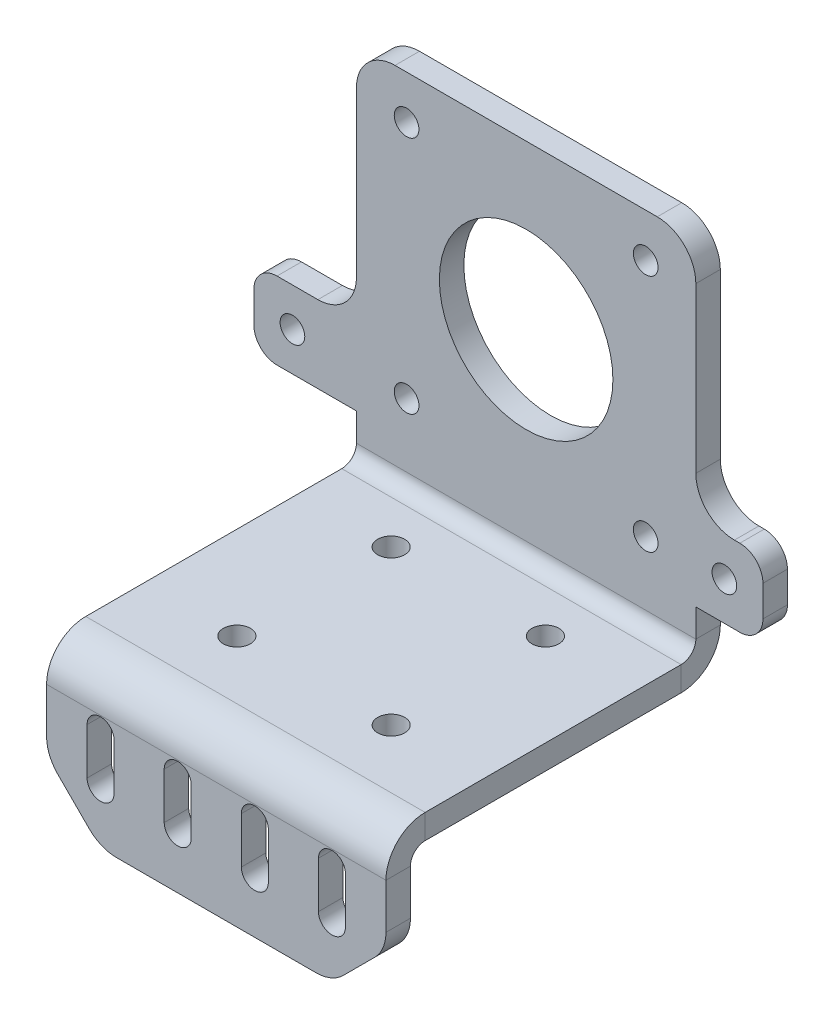
SolidWorks part; units mm, degrees
note: The reader was unsure of these and kept them because the rebuilt part matched: flange length of "Edge-Flange1", "Edge-Flange2".
material "5052-H32"
ref_plane "Front Plane" through (0, 0, 0) normal (0, 0, 1) x (1, 0, 0)
ref_plane "Top Plane" through (0, 0, 0) normal (0, 1, 0) x (1, 0, 0)
ref_plane "Right Plane" through (0, 0, 0) normal (1, 0, 0) x (0, 0, -1)
sketch "Sketch1" plane through (0, 0, 0) normal (0, 1, 0) x (1, 0, 0)
  line L1 (-22, -18.5) -> (22, -18.5)
  line L2 (-22, -18.5) -> (-22, 18.5)
  line L3 (-22, 18.5) -> (22, 18.5)
  line L4 (22, -18.5) -> (22, 18.5)
  line L5 (0, 18.5) -> (0, -18.5) construction
  line L6 (-22, 0) -> (22, 0) construction
  line L7 (-10, -9) -> (10, -9) construction
  line L8 (-10, -9) -> (-10, 11) construction
  line L9 (-10, 11) -> (10, 11) construction
  line L10 (10, -9) -> (10, 11) construction
  line L11 (0, 11) -> (0, -9) construction
  line L12 (-10, 1) -> (10, 1) construction
  circle A0 centre (-10, 11) radius 1.75
  circle A1 centre (10, 11) radius 1.75
  circle A2 centre (10, -9) radius 1.75
  circle A3 centre (-10, -9) radius 1.75
  point P0 (0, 0)
  point P4 (0, 0)
  dimension "D3" = 3.5
  dimension "D1" = 18.5
  dimension "D2" = 44
  dimension "D4" = 20
  dimension "D5" = 1
base flange "Base-Flange1" sketch "Sketch1" thickness 3.175 reverse thickness direction no parameters "D1"=1.905
edge flange "Edge-Flange1" sketch "Sketch8" flange angle 90 flange length 50 flange position material outside bend radius 1.905 thickness 3.175 relief rectangular parameters "D6"=10
sketch "Sketch8" plane through (0, 0, -18.5) normal (0, 0, -1) x (-1, 0, 0)
  line L0 (-22, 0) -> (22, 0) construction
  line L1 (-22, 0) -> (22, 0)
  line L2 (-22, 0) -> (-22, 46.825)
  line L3 (-22, 46.825) -> (22, 46.825)
  line L4 (22, 46.825) -> (22, 0)
bend "EdgeBend1" bend radius 1.905 bend angle 90 parameters "D5"=1
edge flange "Edge-Flange2" sketch "Sketch11" flange angle 90 flange length 20 flange position material outside bend radius 1.905 thickness 3.175 relief rectangular parameters "D6"=10
sketch "Sketch11" plane through (0, -3.175, 18.5) normal (0, 0, 1) x (-1, 0, 0)
  line L0 (22, 0) -> (-22, 0) construction
  line L1 (22, 0) -> (-22, 0)
  line L2 (-22, 0) -> (-22, 16.825)
  line L3 (-22, 16.825) -> (22, 16.825)
  line L4 (22, 16.825) -> (22, 0)
bend "EdgeBend2" bend radius 1.905 bend angle 90 parameters "D5"=2
sketch "Sketch12" plane through (0, 0, -21.675) normal (0, 0, -1) x (-1, 0, 0)
  line L0 (22, 46.825) -> (-22, 46.825) construction
  point P2 (0, 46.825)
  line B0 (0, 41.175) -> (0, 10.175) construction
  line B1 (15.5, 25.675) -> (-15.5, 25.675) construction
  circle B2 centre (0, 25.675) radius 11.25
  circle B3 centre (15.5, 41.175) radius 1.6
  circle B4 centre (15.5, 10.175) radius 1.6
  circle B5 centre (-15.5, 10.175) radius 1.6
  circle B6 centre (-15.5, 41.175) radius 1.6
  dimension "D1" = 21.15
sketch_block_instance "Block-Nema17 Bolt Pattern-1"
sketch_block "Block-Nema17 Bolt Pattern" parameters "D1"=22.5, "D2"=3.2, "D3"=31, "D4"=31
extrude "Cut-Extrude1" cut sketch "Sketch12" against normal up to next normal cut yes
sketch "Sketch13" plane through (0, 0, 21.675) normal (0, 0, 1) x (1, 0, 0)
  line L0 (-22, -9.975) -> (22, -9.975) construction
  line L1 (-22, -5.08) -> (-22, -20) construction
  line L2 (22, -20) -> (22, -5.08) construction
  line L3 (-22, -3.175) -> (22, -3.175) construction
  line L4 (-5, -12.975) -> (-5, -6.975) construction
  line L5 (-6.75, -12.975) -> (-6.75, -6.975)
  line L6 (-3.25, -12.975) -> (-3.25, -6.975)
  line L7 (0, -9.975) -> (0, -20) construction
  line L8 (-22, -20) -> (22, -20) construction
  line L9 (-15, -12.975) -> (-15, -6.975) construction
  line L10 (-16.75, -12.975) -> (-16.75, -6.975)
  line L11 (-13.25, -12.975) -> (-13.25, -6.975)
  line L12 (15, -12.975) -> (15, -6.975) construction
  line L13 (16.75, -12.975) -> (16.75, -6.975)
  line L14 (13.25, -12.975) -> (13.25, -6.975)
  line L15 (5, -12.975) -> (5, -6.975) construction
  line L16 (6.75, -12.975) -> (6.75, -6.975)
  line L17 (3.25, -12.975) -> (3.25, -6.975)
  arc A0 (-6.75, -12.975) -> (-3.25, -12.975) centre (-5, -12.975) ccw
  arc A1 (-3.25, -6.975) -> (-6.75, -6.975) centre (-5, -6.975) ccw
  arc A2 (-16.75, -12.975) -> (-13.25, -12.975) centre (-15, -12.975) ccw
  arc A3 (-13.25, -6.975) -> (-16.75, -6.975) centre (-15, -6.975) ccw
  arc A4 (16.75, -12.975) -> (13.25, -12.975) centre (15, -12.975) cw
  arc A5 (13.25, -6.975) -> (16.75, -6.975) centre (15, -6.975) cw
  arc A6 (6.75, -12.975) -> (3.25, -12.975) centre (5, -12.975) cw
  arc A7 (3.25, -6.975) -> (6.75, -6.975) centre (5, -6.975) cw
  point P10 (-5, -9.975)
  point P22 (-15, -9.975)
  point P29 (15, -9.975)
  point P36 (5, -9.975)
  dimension "D2" = 1.75
  dimension "D1" = 6.8
  dimension "D3" = 6
  dimension "D5" = 10
  dimension "D6" = 5
extrude "Cut-Extrude2" cut sketch "Sketch13" against normal up to next normal cut yes
chamfer "Chamfer1" distance 7 angle 45 2 edges at (-22, -20, 20.0875) (22, -20, 20.0875)
fillet "Fillet1" radius 5 6 edges at (-22, 46.825, -20.0875) (22, 46.825, -20.0875) (22, -13, 20.0875) (15, -20, 20.0875) (-15, -20, 20.0875) (-22, -13, 20.0875)
sketch "Sketch14" plane through (0, 0, -21.675) normal (0, 0, -1) x (-1, 0, 0)
  line L0 (-30.7, 15.525) -> (-30.7, 5.525)
  line L1 (35.3, 5.525) -> (35.3, 15.525)
  line L2 (0, 25.675) -> (0, 10.525) construction
  line L3 (30.3, 10.525) -> (-25.7, 10.525) construction
  line L4 (-22, 15.525) -> (-30.7, 15.525)
  line L5 (-22, 41.825) -> (-22, 1.905) construction
  line L6 (22, 15.525) -> (35.3, 15.525)
  line L7 (22, 1.905) -> (22, 41.825) construction
  line L8 (22, 5.525) -> (35.3, 5.525)
  line L9 (-22, 5.525) -> (-30.7, 5.525)
  line L10 (-22, 15.525) -> (-22, 5.525)
  line L11 (22, 15.525) -> (22, 5.525)
  circle A0 centre (30.3, 10.525) radius 1.6
  circle A1 centre (-25.7, 10.525) radius 1.6
  circle A2 centre (0, 25.675) radius 11.25 construction
  point P0 (0, 25.675)
  dimension "D6" = 5
  dimension "D1" = 3.2
  dimension "D2" = 56
  dimension "D4" = 15.15
  dimension "D5" = 25.7
  dimension "D7" = 5
  dimension "D8" = 5
extrude "Boss-Extrude1" add sketch "Sketch14" against normal up to surface (3.175 mm away) up to face at (-15.5, 39.575, -18.5)
fillet "Fillet2" radius 5 2 edges at (22, 15.525, -20.0875) (-22, 15.525, -20.0875)
fillet "Fillet3" radius 3 4 edges at (-35.3, 5.525, -20.0875) (-35.3, 15.525, -20.0875) (30.7, 5.525, -20.0875) (30.7, 15.525, -20.0875)
sketch "Bend-Lines1" [suppressed] plane through (0, 0, 0) normal (0, 1, 0) x (1, 0, 0)
sketch "Bounding-Box1" [suppressed] plane through (0, 0, 0) normal (0, 1, 0) x (1, 0, 0)
sheet metal parameters "Sheet-Metal1" thickness 3.175 parameters "D1"=1.905
flat pattern "Flat-Pattern1" [suppressed]
sketch "Bend-Lines2" plane through (0, 0, 0) normal (0, 1, 0) x (1, 0, 0)
sketch "Bounding-Box2" [suppressed] plane through (0, 0, 0) normal (0, 1, 0) x (1, 0, 0)
sheet metal parameters "Sheet-Metal2" thickness 3.175 parameters "D1"=1.905
flat pattern "Flat-Pattern1" [suppressed]
sketch "Bend-Lines2" plane through (0, 0, 0) normal (0, 1, 0) x (1, 0, 0)
sketch "Bounding-Box2" [suppressed] plane through (0, 0, 0) normal (0, 1, 0) x (1, 0, 0)
bend of the flat pattern "Flatten-<EdgeBend1>1"
sheet metal parameters "Sheet-Metal3" thickness 3.175 parameters "D1"=1.905
flat pattern "Flat-Pattern1" [suppressed]
sketch "Bend-Lines2" plane through (0, 0, 0) normal (0, 1, 0) x (1, 0, 0)
sketch "Bounding-Box2" [suppressed] plane through (0, 0, 0) normal (0, 1, 0) x (1, 0, 0)
bend of the flat pattern "Flatten-<EdgeBend1>1"
bend of the flat pattern "Flatten-<EdgeBend2>1"
sheet metal parameters "Sheet-Metal4" thickness 3.175 parameters "D1"=1.905
flat pattern "Flat-Pattern1" [suppressed]
sketch "Bend-Lines2" plane through (0, 0, 0) normal (0, 1, 0) x (1, 0, 0)
sketch "Bounding-Box2" [suppressed] plane through (0, 0, 0) normal (0, 1, 0) x (1, 0, 0)
bend of the flat pattern "Flatten-<EdgeBend1>1"
bend of the flat pattern "Flatten-<EdgeBend2>1"
sheet metal parameters "Sheet-Metal5" thickness 3.175 parameters "D1"=1.905
flat pattern "Flat-Pattern1"
sketch "Bend-Lines2" plane through (0, 0, 0) normal (0, 1, 0) x (1, 0, 0)
  line L0 (-22, -18.838) -> (22, -18.838) construction
  line L1 (22, 18.838) -> (-22, 18.838) construction
  line L2 (-22, -18.838) -> (22, -18.838) construction
  line L3 (22, 18.838) -> (-22, 18.838) construction
sketch3d "Bounding-Box2" [suppressed]
  line L0 (22, -36.501, 0) -> (22, 66.501, 0) construction
  line L1 (-22, -36.501, 0) -> (-22, 66.501, 0) construction
  line L2 (22, -36.501, 0) -> (-22, -36.501, 0) construction
  line L3 (22, 66.501, 0) -> (-22, 66.501, 0) construction
bend of the flat pattern "Flatten-<EdgeBend1>1"
bend of the flat pattern "Flatten-<EdgeBend2>1"
sheet metal parameters "Sheet-Metal6" thickness 3.175 parameters "D1"=1.905
flat pattern "Flat-Pattern1"
sketch "Bend-Lines2" plane through (0, 0, 0) normal (0, 1, 0) x (1, 0, 0)
  line L0 (-22, -19.338) -> (22, -19.338) construction
  line L1 (22, 19.338) -> (-22, 19.338) construction
  line L2 (-22, -19.338) -> (22, -19.338) construction
  line L3 (22, 19.338) -> (-22, 19.338) construction
sketch3d "Bounding-Box2" [suppressed]
  line L0 (30.7, -37.001, 0) -> (30.7, 67.001, 0) construction
  line L1 (-35.3, -37.001, 0) -> (-35.3, 67.001, 0) construction
  line L2 (30.7, -37.001, 0) -> (-35.3, -37.001, 0) construction
  line L3 (30.7, 67.001, 0) -> (-35.3, 67.001, 0) construction
bend of the flat pattern "Flatten-<EdgeBend1>1"
bend of the flat pattern "Flatten-<EdgeBend2>1"
equation "\"D6@Sketch13\"=\"D5@Sketch13\"/2"
equation "\"D8@Sketch14\"=\"D7@Sketch14\""
